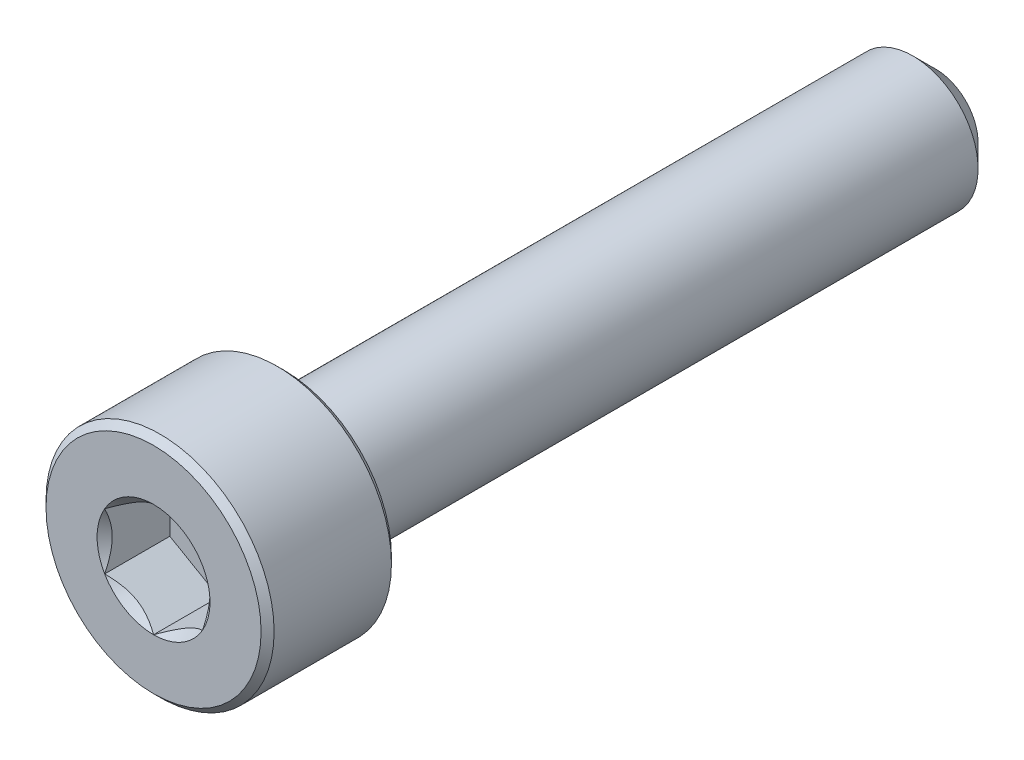
SolidWorks part; units mm, degrees
material "Alloy Steel"
ref_plane "Front Plane" through (0, 0, 0) normal (0, 0, 1) x (1, 0, 0)
ref_plane "Top Plane" through (0, 0, 0) normal (0, 1, 0) x (1, 0, 0)
ref_plane "Right Plane" through (0, 0, 0) normal (1, 0, 0) x (0, 0, -1)
sketch "Sketch1" plane through (0, 0, 0) normal (1, 0, 0) x (0, 0, -1)
  line L0 (-12, 0) -> (12, 0) construction
  line L1 (12, 0) -> (12, 1.3) construction
  line L2 (12, 1.3) -> (11.3, 2) construction
  line L3 (11.3, 2) -> (-8, 2) construction
  line L5 (-8, 2) -> (-8, 3.5) construction
  line L6 (-8, 3.5) -> (-12, 3.5) construction
  line L7 (-12, 3.5) -> (-12, 0) construction
  line L8 (12, 1.3) -> (12, 2) construction
  line L9 (11.9563, 2.0758) -> (12.3063, 1.4696) construction
  line L10 (12.3063, 1.4696) -> (12.6562, 2.0758) construction
  line L11 (12.6562, 2.0758) -> (11.9563, 2.0758) construction
  line L12 (12.3063, 2.0758) -> (12.3063, 2) construction
  line L13 (12.3063, 1.4696) -> (12.3063, 1.5453) construction
  line L14 (12.2625, 1.5453) -> (12.35, 1.5453) construction
  line L15 (12, 2) -> (12.6125, 2) construction
  line L16 (11.9781, 2.0379) -> (12.6344, 2.0379) construction
  line L17 (12, 0) -> (12, -2) construction
  line L18 (-8.2, 3.5) -> (-8, 3.3) construction
  line L19 (-11.8, 3.5) -> (-12, 3.3) construction
  point P0 (-12, 1.5)
  point P3 (9.55, 2)
  point P4 (0, 0)
  point P22 (12.3063, 1.5453)
  point P24 (-8, 2)
  point P25 (12.3063, 2)
  point P28 (12.3063, 2.0379)
  point P29 (9.55, -2)
  point P31 (-10, 3.5)
  point P37 (-8.7, 3.5)
  point P38 (-11.7, 3.5)
  point P41 (-10, 0)
  dimension "head height" = 4
  dimension "D1" = 45
  dimension "Head Diameter" = 7
  dimension "Thread Size" = 4
  dimension "drive size" = 3
  dimension "Thread Pitch" = 0.7
  dimension "D2" = 0.0875
  dimension "D3" = 0.7
  dimension "D4" = 2.45
  dimension "D7" = 0.2
  dimension "D8" = 0.2
  dimension "D9" = 0.2
  dimension "D10" = 0.1
  dimension "D11" = 0.5
  dimension "length" = 20
  dimension "Drive Depth" = 2
sketch "Sketch2" plane through (0, 0, 0) normal (1, 0, 0) x (0, 0, -1)
  line L1 (-11.8, 3.5) -> (-8.2, 3.5)
  line L4 (11.3, 2) -> (12, 1.3)
  line L5 (12, 1.3) -> (12, 0)
  line L6 (-8.2, 3.5) -> (-8, 3.3) construction
  line L7 (12, 0) -> (-12, 0)
  line L8 (-11.8, 3.5) -> (-12, 3.3) construction
  line L9 (-8.2, 3.5) -> (-8, 3.3)
  line L10 (-11.8, 3.5) -> (-12, 3.3)
  line L11 (-12, 3.3) -> (-12, 0)
  line L12 (-8, 3.3) -> (-8, 2)
  line L13 (-8, 2) -> (11.3, 2)
revolve "Revolve1" add sketch "Sketch2" angle 360 about L7
sketch "Sketch3" plane through (0, 0, 12) normal (0, 0, 1) x (1, 0, 0)
  line L1 (0, 1.7321) -> (-1.5, 0.866)
  line L2 (-1.5, 0.866) -> (-1.5, -0.866)
  line L3 (-1.5, -0.866) -> (0, -1.7321)
  line L4 (0, -1.7321) -> (1.5, -0.866)
  line L5 (1.5, -0.866) -> (1.5, 0.866)
  line L6 (1.5, 0.866) -> (0, 1.7321)
  circle A0 centre (0, 0) radius 1.5 construction
  dimension "D1" = 3
extrude "Cut-Extrude1" cut sketch "Sketch3" against normal up to vertex (2 mm away) up to point (0, 0, 10)
sketch "Sketch4" plane through (0, 0, 12) normal (0, 0, 1) x (1, 0, 0)
  circle A0 centre (0, 0) radius 1.7321
extrude "Cut-Extrude2" cut sketch "Sketch4" against normal blind 0.5 draft 45
ref_plane "Plane1" [suppressed] through (0, 0, 8) normal (0, 0, 1) x (1, 0, 0)
split "Split1" [suppressed] bodies to split 106
sketch "Sketch6" [suppressed] plane through (0, 0, -12) normal (0, 0, -1) x (-1, 0, 0)
  circle A0 centre (0, 0) radius 2
curve "Helix/Spiral1" [suppressed] pitch 0.7 height 20.7 turns 29.5714
sketch "Sketch7" [suppressed] plane through (0, 0, 0) normal (1, 0, 0) x (0, 0, -1)
  line L0 (11.9781, 2.0379) -> (12.6344, 2.0379)
  line L1 (12.6344, 2.0379) -> (12.35, 1.5453)
  line L2 (12.35, 1.5453) -> (12.2625, 1.5453)
  line L3 (12.2625, 1.5453) -> (11.9781, 2.0379)
sweep "Cut-Sweep1" [suppressed] cut profiles "Sketch7" path "Helix/Spiral1"
sketch "Sketch8" [suppressed] plane through (0, 0, 8) normal (0, 0, -1) x (-1, 0, 0)
  circle A0 centre (0, 0) radius 2
extrude "Boss-Extrude1" [suppressed] add sketch "Sketch8" along normal through all draft 45
ref_plane "Plane2" [suppressed] through (0, 0, 10) normal (0, 0, 1) x (1, 0, 0)
sketch "Sketch9" [suppressed] plane through (0, 0, 10) normal (0, 0, 1) x (1, 0, 0)
  line L0 (0, 3.4038) -> (0.0916, 3.4988)
  line L1 (0, 3.4038) -> (-0.0916, 3.4988)
  line L2 (0, 3.5) -> (0, 0) construction
  line L3 (-0.0916, 3.4988) -> (0, 0) construction
  line L4 (0, 0) -> (0.0916, 3.4988) construction
  arc A0 (0.0916, 3.4988) -> (-0.0916, 3.4988) centre (0, 0) ccw
  circle A1 centre (0, 0) radius 3.4038 construction
  dimension "D1" = 7
  dimension "D2" = 6.8075
  dimension "D3" = 3
extrude "Cut-Extrude4" [suppressed] cut sketch "Sketch9" against normal up to vertex and the other way up to vertex
pattern_circular "CirPattern2" [suppressed] count 96 over 360 about axis through (0, 0, 12) along (0, 0, -1) of bodies 113
equation "\"D2@Sketch1\" = \"Thread Pitch@Sketch1\" / 8"
equation "\"D3@Sketch1\" = \"Thread Pitch@Sketch1\""
equation "\"D3@Helix/Spiral1\" = \"length@Sketch1\" + \"Thread Pitch@Sketch1\""
equation "\"D4@Helix/Spiral1\" = \"Thread Pitch@Sketch1\""
equation "\"D4@Sketch1\" = \"Thread Pitch@Sketch1\" * 3.5"
equation "\"D7@Sketch1\"=\"head height@Sketch1\"*.05"
equation "\"D8@Sketch1\"=\"D7@Sketch1\""
equation "\"D9@Sketch1\"=\"D7@Sketch1\""
equation "\"D10@Sketch1\"=\"D7@Sketch1\"/2"
equation "\"D11@Sketch1\"=\"D10@Sketch1\"*5"
equation "\"D1@CirPattern2\"=( 360 / \"D3@Sketch9\" )*0.8"
equation "\"D1@Sketch3\" = \"drive size@Sketch1\""
equation "\"D2@Sketch9\"=\"Head Diameter@Sketch1\" * 0.9725"
